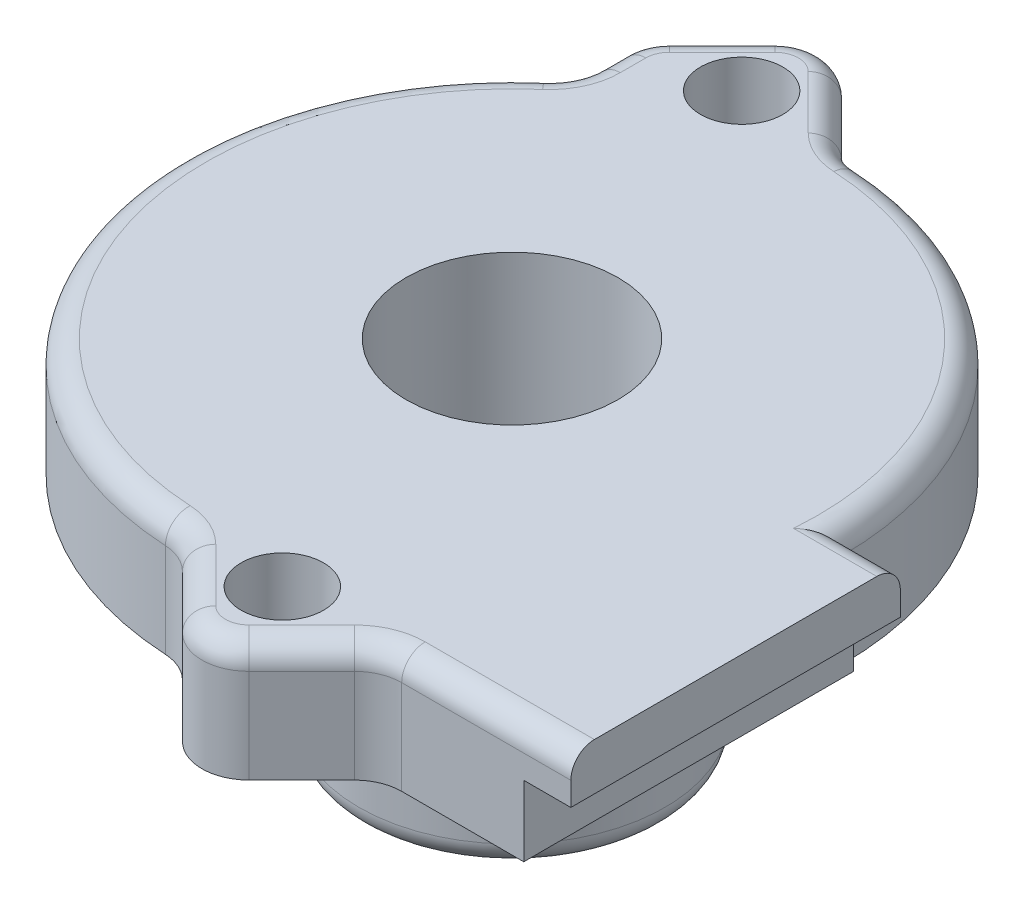
SolidWorks part; units mm, degrees
ref_plane "Front Plane" through (0, 0, 0) normal (0, 0, 1) x (1, 0, 0)
ref_plane "Top Plane" through (0, 0, 0) normal (0, 1, 0) x (1, 0, 0)
ref_plane "Right Plane" through (0, 0, 0) normal (1, 0, 0) x (0, 0, -1)
sketch "Sketch1" plane through (0, 0, 0) normal (0, 1, 0) x (1, 0, 0)
  circle A0 centre (0, 0) radius 14
  circle A1 centre (0, 0) radius 4.5
  dimension "D1" = 28
  dimension "D2" = 9
extrude "Boss-Extrude1" add sketch "Sketch1" along normal blind 5
sketch "Sketch5" plane through (0, 5, 0) normal (0, 1, 0) x (1, 0, 0)
  line L0 (0, -14) -> (4.2426, -18.2426)
  line L1 (14.5, -14) -> (14.5, 0)
  line L2 (14.5, 0) -> (14, 0)
  line L3 (14, 0) -> (0, -14)
  line L4 (4.2426, -18.2426) -> (8.4853, -14)
  line L5 (-55, 0) -> (55, 0) construction
  line L6 (0, -55) -> (0, 55) construction
  line L7 (8.4853, -14) -> (14.5, -14)
  line L8 (0, 14) -> (-4.2426, 18.2426)
  line L9 (-4.2426, 18.2426) -> (-8.4853, 14)
  line L10 (-8.4853, 14) -> (-8.4853, 11.1355)
  line L11 (-8.4853, 11.1355) -> (0, 14)
  circle A2 centre (0, 0) radius 14 construction
  dimension "D1" = 14.5
  dimension "D2" = 6
  dimension "D3" = 6
  dimension "D4" = 90
  dimension "D5" = 6
  dimension "D6" = 6
  dimension "D7" = 135
extrude "Boss-Extrude3" add sketch "Sketch5" against normal blind 5
sketch "Sketch6" plane through (0, 0, 0) normal (0, -1, 0) x (1, 0, 0)
  circle A0 centre (0, 0) radius 4.5
  circle A1 centre (0, 0) radius 6.5
  circle A2 centre (0, 0) radius 4.5 construction
  dimension "D1" = 2
extrude "Boss-Extrude4" add sketch "Sketch6" along normal blind 10
sketch "Sketch9" plane through (0, 5, 0) normal (0, 1, 0) x (1, 0, 0)
  line L0 (4.2426, -18.2426) -> (8.4853, -14) construction
  line L1 (0, -14) -> (4.2426, -18.2426) construction
  line L2 (-4.2426, 18.2426) -> (-8.4853, 14) construction
  line L3 (0, 14) -> (-4.2426, 18.2426) construction
  circle A0 centre (4.2426, -14) radius 1.75
  circle A1 centre (-4.2426, 14) radius 1.75
  dimension "D1" = 3.5
  dimension "D2" = 3
  dimension "D3" = 3
  dimension "D5" = 3
  dimension "D4" = 3
extrude "Cut-Extrude2" cut sketch "Sketch9" against normal blind 10
sketch "Sketch11" plane through (14.5, 0, 0) normal (1, 0, 0) x (0, 0, -1)
  line L0 (0, 0) -> (0, 5) construction
  line L1 (-14, 5) -> (0, 5)
  line L2 (-14, 5) -> (-14, 3)
  line L3 (-14, 3) -> (0, 3)
  line L4 (0, 5) -> (0, 3)
  dimension "D1" = 2
extrude "Boss-Extrude5" add sketch "Sketch11" along normal blind 2
fillet "Fillet1" radius 2 7 edges at (0, 2.5, 14) (8.4853, 2.5, 14) (4.2426, 2.5, 18.2426) (-8.4853, 2.5, -11.1355) (-8.4853, 2.5, -14) (0, 2.5, -14) (-4.2426, 2.5, -18.2426)
fillet "Fillet2" radius 1 19 edges at (10.1594, 5, -9.6326) (0.0368, 5, -14.1506) (-1.6958, 5, -15.6958) (-4.2426, 5, -17.4142) (-6.7782, 5, -15.7071) (-8.333, 5, -13.9369) (-8.4853, 5, -12.6285) (-8.6658, 5, -11.2552) (12.9069, 5, 14) (8.5483, 5, 14.1522) (6.7782, 5, 15.7071) (4.2426, 5, 17.4142) (1.6958, 5, 15.6958) (-0.0368, 5, 14.1506) (0, -10, -6.5) (0, -10, -4.5) (0, 0, 6.5) (15.25, 5, 0) (-13.2414, 5, 4.5459)
